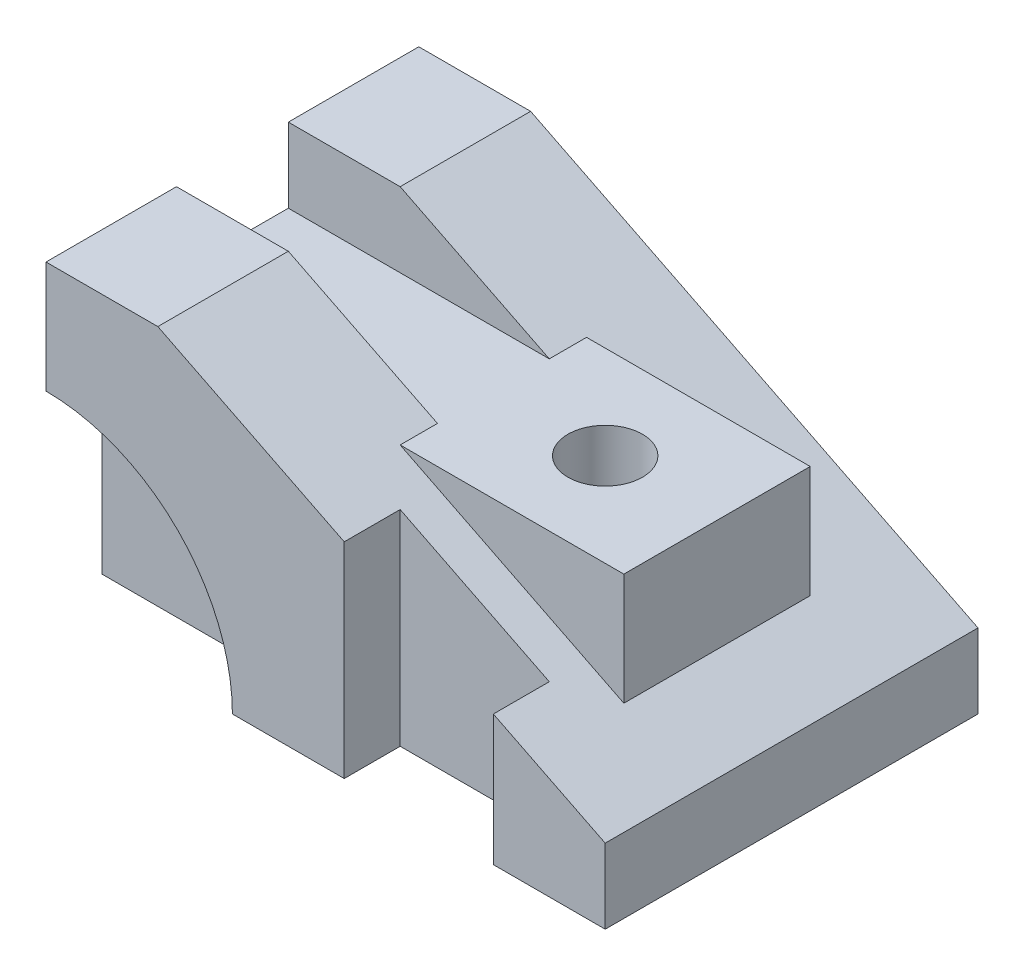
SolidWorks part; units mm, degrees
ref_plane "Front Plane" through (0, 0, 0) normal (0, 0, 1) x (1, 0, 0)
ref_plane "Top Plane" through (0, 0, 0) normal (0, 1, 0) x (1, 0, 0)
ref_plane "Right Plane" through (0, 0, 0) normal (1, 0, 0) x (0, 0, -1)
sketch "Sketch1" plane through (0, 0, 0) normal (0, 0, 1) x (1, 0, 0)
  line L0 (0, 80) -> (30, 80)
  line L1 (30, 80) -> (70, 60)
  line L2 (70, 60) -> (130, 60)
  line L3 (130, 60) -> (130, 30)
  line L4 (130, 30) -> (150, 20)
  line L5 (150, 20) -> (150, 0)
  line L6 (150, 0) -> (0, 0)
  line L7 (0, 0) -> (0, 80)
  line L8 (70, 60) -> (130, 30) construction
  dimension "D1" = 80
  dimension "D2" = 150
  dimension "D3" = 20
  dimension "D4" = 30
  dimension "D5" = 20
  dimension "D6" = 30
extrude "Boss-Extrude1" add sketch "Sketch1" along normal mid plane 100 contours L8 L1 L0 L7 L6 L5 L4 region at (60, 31.4286, 0)
extrude "Boss-Extrude2" add sketch "Sketch1<3>" along normal mid plane 50 contours L2 L8 L3 region at (110, 50, 0)
sketch "Sketch1<3>" plane through (0, 0, 0) normal (0, 0, 1) x (1, 0, 0) same geometry as "Sketch1"
sketch "Sketch2" plane through (0, 0, 0) normal (0, 1, 0) x (1, 0, 0)
  line L0 (80, -50) -> (80, -35)
  line L2 (80, -35) -> (120, -35)
  line L3 (120, -35) -> (120, -50)
  line L4 (0, 15) -> (0, -15)
  line L5 (70, -25) -> (70, 25) construction
  line L6 (70, 15) -> (0, 15)
  line L7 (0, -50) -> (0, 50) construction
  line L8 (70, -15) -> (70, 15)
  line L9 (70, -15) -> (0, -15)
  line L11 (150, -50) -> (150, 50) construction
  line L12 (30, -50) -> (150, -50) construction
  line L13 (80, -50) -> (120, -50)
  line L14 (130, -25) -> (130, 25) construction
  circle A0 centre (100, 0) radius 10
  point P4 (0, 0)
  point P23 (0, 0)
  point P24 (130, 0)
  dimension "D5" = 20
  dimension "D1" = 15
  dimension "D2" = 40
  dimension "D3" = 30
  dimension "D4" = 30
  dimension "D6" = 30
extrude "Cut-Extrude1" cut sketch "Sketch2" against normal up to surface (-60 mm away) from surface contours L9 L8 L6 L4 region at (35, 0, 0) up to face at (100, 60, 0) starting at face at (15, 80, 0)
extrude "Cut-Extrude2" cut sketch "Sketch2<3>" along normal through all contours L2 L3 L13 L0
sketch "Sketch2<3>" plane through (0, 0, 0) normal (0, 1, 0) x (1, 0, 0) same geometry as "Sketch2"
extrude "Cut-Extrude3" cut sketch "Sketch2<4>" against normal through all both and the other way through all contours A0 region at (100, 0, 0)
sketch "Sketch2<4>" plane through (0, 0, 0) normal (0, 1, 0) x (1, 0, 0) same geometry as "Sketch2"
sketch "Sketch3" plane through (0, 0, 0) normal (0, 0, 1) x (1, 0, 0)
  circle A0 centre (0, 0) radius 50
  dimension "D1" = 100
extrude "Cut-Extrude4" cut sketch "Sketch3" against normal blind 15 and the other way through all from surface starting at face at (38, 43, 50)
